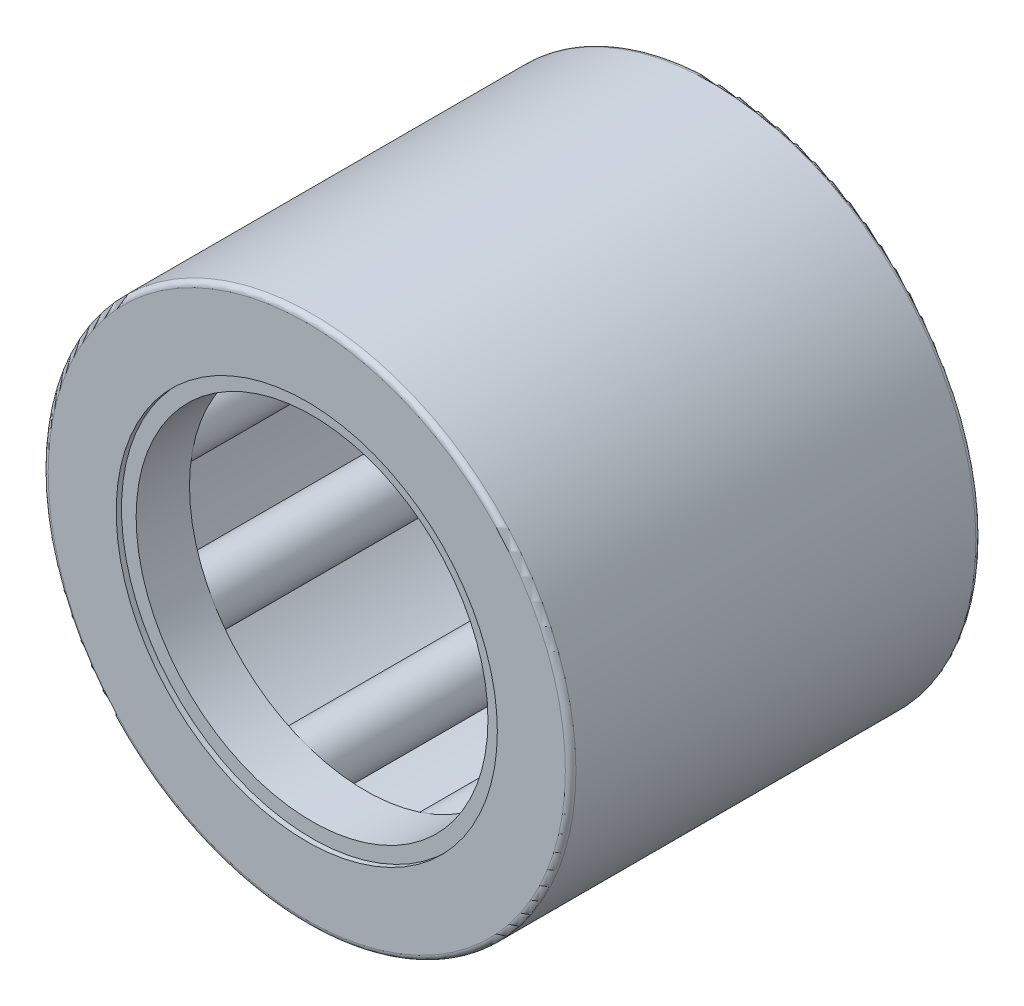
SolidWorks part; units mm, degrees
material "AISI 4140 Steel, annealed"
ref_plane "Front Plane" through (0, 0, 0) normal (0, 0, 1) x (1, 0, 0)
ref_plane "Top Plane" through (0, 0, 0) normal (0, 1, 0) x (1, 0, 0)
ref_plane "Right Plane" through (0, 0, 0) normal (1, 0, 0) x (0, 0, -1)
sketch "Sketch1" plane through (0, 0, 0) normal (1, 0, 0) x (0, 0, -1)
  line L0 (-5.5563, 0) -> (5.5562, 0) construction
  line L1 (0, 0) -> (0, 7.1438) construction
  line L2 (-5.5563, 0) -> (-5.5563, 7.1438) construction
  line L3 (-5.5563, 7.1438) -> (5.5563, 7.1438)
  line L4 (5.5563, 7.1438) -> (5.5562, 0) construction
  line L5 (5.5562, 0) -> (4.7625, 0) construction
  line L6 (4.7625, 0) -> (4.7625, 6.35) construction
  line L7 (4.7625, 6.35) -> (-4.7625, 6.35)
  line L8 (-4.7625, 6.35) -> (-4.7625, 0) construction
  line L9 (-4.7625, 0) -> (-5.5563, 0) construction
  line L10 (-5.5563, 7.1438) -> (-5.5563, 5.1594)
  line L11 (-5.5563, 5.1594) -> (-4.7625, 5.1594)
  line L12 (-4.7625, 5.1594) -> (-4.7625, 6.35)
  line L13 (4.7625, 7.1438) -> (4.7625, 6.35) construction
  line L14 (4.7625, 6.35) -> (4.7625, 5.1594)
  line L15 (4.7625, 5.1594) -> (5.5563, 5.1594)
  line L16 (5.5563, 5.1594) -> (5.5563, 7.1438)
  line L17 (4.7625, 6.35) -> (4.7625, 5.5563) construction
  line L18 (4.7625, 5.5563) -> (4.7625, 4.7625) construction
  point P5 (0, 4.7625)
  dimension "Width" = 11.1125
  dimension "OD" = 14.2875
  dimension "Shaft Dia" = 9.525
revolve "Revolve1" add sketch "Sketch1" angle 360 about L0
sketch "Sketch2" plane through (0, 0, 0) normal (1, 0, 0) x (0, 0, -1)
  line L0 (4.7625, 6.35) -> (-4.7625, 6.35) construction
  line L1 (-3.9687, 5.5563) -> (3.9687, 5.5563) construction
  line L2 (-3.9687, 5.5563) -> (-3.9687, 6.35) construction
  line L3 (-3.9687, 6.35) -> (3.9687, 6.35)
  line L4 (3.9687, 5.5563) -> (3.9687, 6.35) construction
  line L5 (4.7625, 5.1594) -> (5.5563, 5.1594) construction
  line L6 (-4.7625, 5.5563) -> (-3.9687, 5.5563) construction
  line L7 (3.9687, 5.5563) -> (4.7625, 5.5563) construction
  line L8 (-5.5563, 5.1594) -> (-4.7625, 5.1594) construction
  line L9 (-3.9687, 5.7547) -> (-3.9687, 5.3578) construction
  line L10 (-4.7625, 5.5563) -> (-4.7625, 5.1594) construction
  line L11 (-3.9687, 6.35) -> (-3.9687, 5.7547)
  line L12 (3.9687, 6.35) -> (3.9687, 5.7547)
  line L13 (3.9687, 5.7547) -> (-3.9687, 5.7547)
  line L14 (0, 6.35) -> (0, 4.7625) construction
  line L15 (-4.7625, 5.1594) -> (-4.7625, 6.35) construction
  line L16 (-3.9687, 5.3578) -> (-4.7625, 5.3578) construction
  line L17 (0, 0) -> (5.5563, 0) construction
  line L31 (5.5563, -7.1438) -> (5.5563, 7.1438) construction
  point P16 (0, 5.5563)
revolve "Revolve2" add sketch "Sketch2" angle 360 about L1
sketch "Sketch3" plane through (0, 0, 0) normal (1, 0, 0) x (0, 0, -1)
  line L0 (4.7625, 6.35) -> (4.7625, 5.1594) construction
  line L1 (-4.7625, 5.5563) -> (4.7625, 5.5563)
  line L2 (-4.7625, 5.5563) -> (-4.7625, 5.7547)
  line L3 (-4.7625, 5.7547) -> (4.7625, 5.7547)
  line L4 (4.7625, 5.5563) -> (4.7625, 5.7547)
  line L5 (0, 0) -> (5.5563, 0) construction
  line L6 (5.5563, -7.1438) -> (5.5563, 7.1438) construction
revolve "Revolve3" add sketch "Sketch3" angle 360 about L1
ref_axis "Axis1" through (0, 0, -5.5562) along (0, 0, 1)
pattern_circular "CirPattern1" count 9 every 40 about axis through (0, 0, -5.5562) along (0, 0, 1) of bodies 166 167
fillet "Fillet1" radius 0.1429 2 edges at (7.1438, 0, -5.5563) (7.1438, 0, 5.5563)
sketch "Sketch4" plane through (0, 0, 0) normal (1, 0, 0) x (0, 0, -1)
  line L1 (5.4134, 4.7625) -> (3.9687, 4.7625)
  line L2 (5.4134, 4.7625) -> (5.4134, 5.1594)
  line L3 (5.4134, 5.1594) -> (3.9687, 5.1594)
  line L4 (3.9687, 4.7625) -> (3.9687, 5.1594)
  line L5 (-5.5563, 5.1594) -> (-4.7625, 5.1594) construction
  line L6 (5.4134, -7.1438) -> (5.4134, 7.1438) construction
  line L7 (3.9687, 6.35) -> (3.9687, 5.7547) construction
revolve "Revolve4" add sketch "Sketch4" angle 360 about L0
sketch "Sketch5" plane through (0, 0, 0) normal (1, 0, 0) x (0, 0, -1)
  line L0 (-5.4134, 7.1438) -> (-5.4134, -7.1438) construction
  line L1 (-3.9687, 4.7625) -> (-5.4134, 4.7625)
  line L2 (-3.9687, 4.7625) -> (-3.9687, 5.1594)
  line L3 (-3.9687, 5.1594) -> (-5.4134, 5.1594)
  line L4 (-5.4134, 4.7625) -> (-5.4134, 5.1594)
  line L6 (-3.9687, 6.35) -> (-3.9687, 5.7547) construction
  line L7 (-5.5563, 5.1594) -> (-4.7625, 5.1594) construction
revolve "Revolve5" add sketch "Sketch5" angle 360 about L0
sketch "Front View" plane through (0, 0, 0) normal (0, 0, 1) x (1, 0, 0)
  circle A0 centre (0, 0) radius 4.7625 construction
  circle A1 centre (0, 0) radius 7.1438 construction
  dimension "OD" = 14.2875
  dimension "ID" = 9.525
sketch "Right View" plane through (0, 0, 0) normal (1, 0, 0) x (0, 0, -1)
  line L0 (-5.5562, 7.1438) -> (5.5562, 7.1438) construction
  dimension "Width" = 11.1125
ref_axis "Center Axis 1" through (0, 0, -5.4134) along (0, 0, 1)
ref_plane "Contact Plane 1" through (0, 0, 5.5563) normal (0, 0, 1) x (1, 0, 0)
ref_plane "Contact Plane 2" through (0, 0, -5.5563) normal (0, 0, -1) x (-1, 0, 0)
equation "\"Rollers@CirPattern1\" = \"OD@Sketch1\"*16"
equation "\"D1@Fillet1\" = \"OD@Sketch1\"*.01"
equation "\"Angle@CirPattern1\"= 360 / \"Rollers@CirPattern1\""
equation "\"OD@Front View\"=\"OD@Sketch1\""
equation "\"ID@Front View\"=\"Shaft Dia@Sketch1\""
equation "\"Width@Right View\"=\"Width@Sketch1\""
